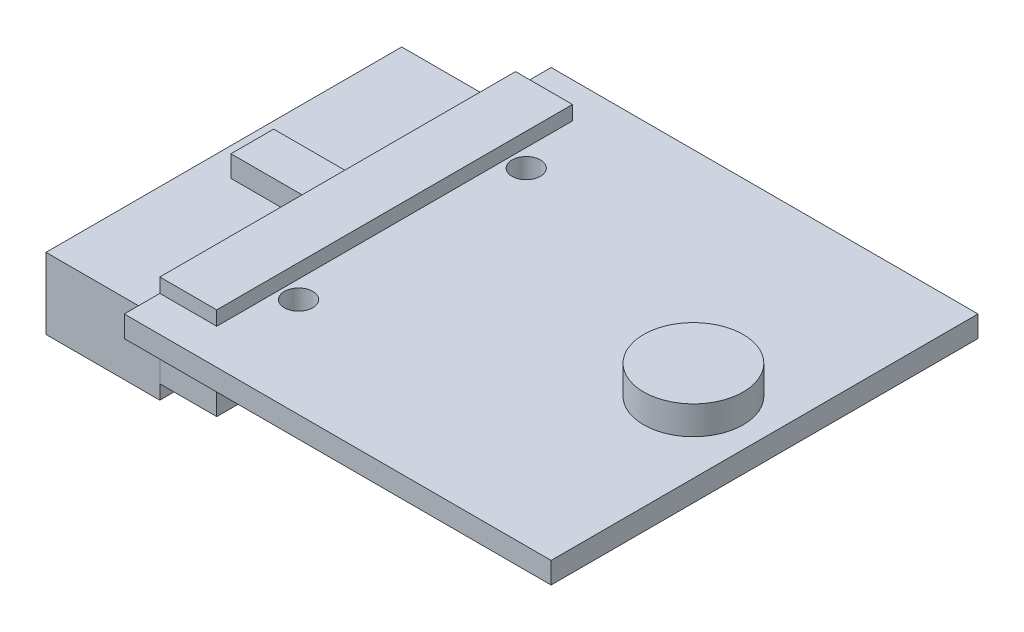
SolidWorks part; units mm, degrees
ref_plane "Front" through (0, 0, 0) normal (0, 0, 1) x (1, 0, 0)
ref_plane "Top" through (0, 0, 0) normal (0, 1, 0) x (1, 0, 0)
ref_plane "Right" through (0, 0, 0) normal (1, 0, 0) x (0, 0, -1)
sketch "Эскиз1" plane through (0, 0, 0) normal (0, 1, 0) x (1, 0, 0)
  line L0 (-15, -1.5) -> (-21, -1.5)
  line L1 (-15, 15) -> (15, 15)
  line L2 (-15, 15) -> (-15, -15)
  line L3 (-15, -15) -> (15, -15)
  line L4 (15, 15) -> (15, -15)
  line L5 (-15, 15) -> (15, -15) construction
  line L6 (-15, -15) -> (15, 15) construction
  line L7 (-21, -1.5) -> (-21, 1.5)
  line L8 (-21, 1.5) -> (-15, 1.5)
  line L9 (-15, 12.5) -> (-11, 12.5)
  line L10 (-15, 12.5) -> (-23, 12.5)
  line L11 (-15, 12.5) -> (-15, -12.5)
  line L12 (-15, -12.5) -> (-23, -12.5)
  line L13 (-23, 12.5) -> (-23, -12.5)
  line L14 (-11, 12.5) -> (-11, -12.5)
  line L15 (-11, -12.5) -> (-15, -12.5)
  circle A0 centre (10, 0) radius 3.5
  circle A1 centre (-9.75, -8) radius 1
  circle A2 centre (-9.75, 8) radius 1
  point P0 (0, 0)
  dimension "D6" = 7
  dimension "D13" = 2
  dimension "D14" = 2
  dimension "D1" = 30
  dimension "D2" = 30
  dimension "D3" = 3
  dimension "D4" = 13.5
  dimension "D5" = 6
  dimension "D7" = 5
  dimension "D8" = 15
  dimension "D9" = 25
  dimension "D10" = 8
  dimension "D11" = 2.5
  dimension "D12" = 4
  dimension "D15" = 7
  dimension "D16" = 7
  dimension "D17" = 1.25
  dimension "D18" = 1.25
extrude "Бобышка-Вытянуть1" add sketch "Эскиз1" along normal blind 1.5 contours L14 L15 L2 L3 L4 L1 L9 A0 | L15 L14 L9 L2 | L8 L7 L0 L2 | A0 region at (-18, 0, 0) region at (-13, 0, 0) region at (1.2929, 0, 0) region at (10, 0, 0)
extrude "Бобышка-Вытянуть2" add sketch "Эскиз1<3>" against normal blind 5 separate body contours L10 L13 L12 L2 L0 L7 L8 | L8 L7 L0 L2 region at (-15.2625, 0, 7) region at (-18, 0, 0)
sketch "Эскиз1<3>" plane through (0, 0, 0) normal (0, 1, 0) x (1, 0, 0) same geometry as "Эскиз1"
extrude "Бобышка-Вытянуть3" add sketch "Эскиз1<4>" against normal blind 4 and the other way blind 2.5 separate body contours L15 L14 L9 L2 region at (-13, 0, 0)
sketch "Эскиз1<4>" plane through (0, 0, 0) normal (0, 1, 0) x (1, 0, 0) same geometry as "Эскиз1"
extrude "Бобышка-Вытянуть4" add sketch "Эскиз1<5>" along normal blind 3.5 contours A0
sketch "Эскиз1<5>" plane through (0, 0, 0) normal (0, 1, 0) x (1, 0, 0) same geometry as "Эскиз1"
